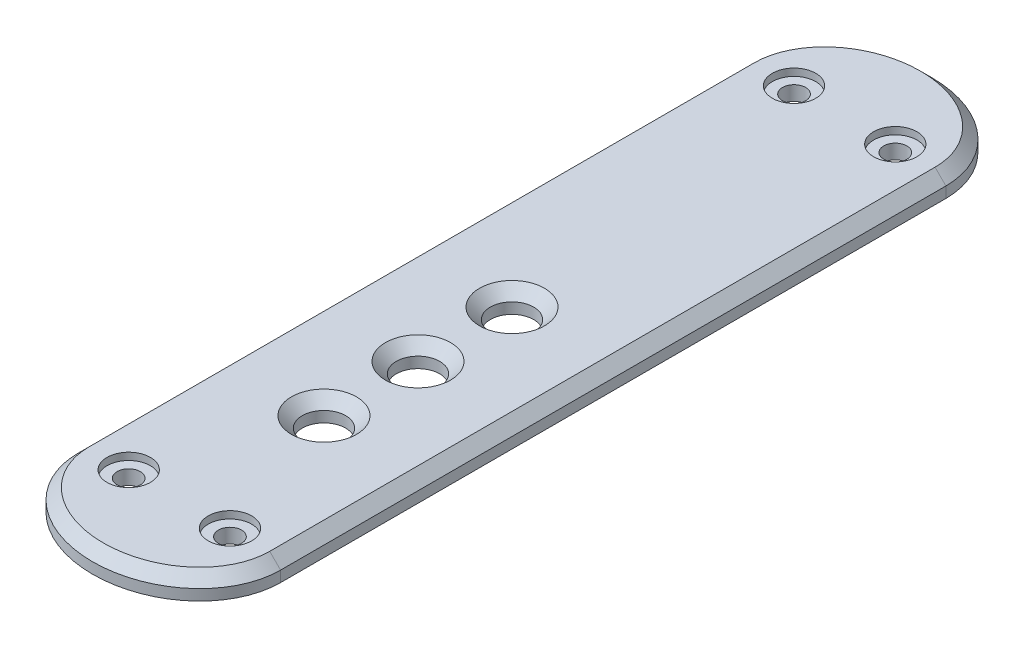
SolidWorks part; units mm, degrees
ref_plane "Front Plane" through (0, 0, 0) normal (0, 0, 1) x (1, 0, 0)
ref_plane "Top Plane" through (0, 0, 0) normal (0, 1, 0) x (1, 0, 0)
ref_plane "Right Plane" through (0, 0, 0) normal (1, 0, 0) x (0, 0, -1)
sketch "Sketch3" plane through (0, 0, 0) normal (0, 1, 0) x (1, 0, 0)
  line L0 (-7, 0) -> (7, 0) construction
  line L4 (-7, -23) -> (-7, 23)
  line L5 (0, -29) -> (0, 29) construction
  line L6 (7, -23) -> (7, 23)
  circle A0 centre (-3.5, 23) radius 0.8
  circle A1 centre (-3.5, 23) radius 1.5
  circle A2 centre (3.5, 23) radius 1.5
  circle A3 centre (3.5, 23) radius 0.8
  circle A4 centre (3.5, -23) radius 0.8
  circle A5 centre (3.5, -23) radius 1.5
  circle A6 centre (-3.5, -23) radius 1.5
  circle A7 centre (-3.5, -23) radius 0.8
  ellipse E0 centre (0, 23) end of major axis (-7, 23) minor radius 6 (7, 23) -> (-7, 23) ccw
  ellipse E1 centre (0, -23) end of major axis (-7, -23) minor radius 6 (7, -23) -> (-7, -23) cw
  point P20 (0, 0)
  dimension "D1" = 1.6
  dimension "D6" = 3
  dimension "D2" = 3.5
  dimension "D3" = 23
  dimension "D4" = 29
  dimension "D5" = 7
extrude "Boss-Extrude2" add sketch "Sketch3" against normal blind 1.5 contours L4 E0 L6 E1
extrude "Cut-Extrude1" cut sketch "Sketch3<3>" against normal through all contours A7 | A4 | A0 | A3
sketch "Sketch3<3>" plane through (0, 0, 0) normal (0, 1, 0) x (1, 0, 0) same geometry as "Sketch3"
extrude "Cut-Extrude4" cut sketch "Sketch3<4>" against normal blind 0.5 contours A1 | A2 | A6 | A5
sketch "Sketch3<4>" plane through (0, 0, 0) normal (0, 1, 0) x (1, 0, 0) same geometry as "Sketch3"
chamfer "Chamfer2" distance 0.75 angle 45 4 edges at (7, 0, 0) (0, 0, 29) (0, 0, -29) (-7, 0, 0)
sketch "Sketch6" plane through (0, 0, 0) normal (0, 1, 0) x (1, 0, 0)
  line L0 (0, 11.45) -> (0, 14.1085)
  line L1 (0.2205, 14.1892) -> (1.4045, 12.7884)
  line L2 (1.5955, 12.7884) -> (2.7795, 14.1892)
  line L3 (3, 14.1085) -> (3, 11.45)
  line L4 (-2.9, 11.45) -> (3, 11.45) construction
  line L13 (-3.5, 21.5) -> (3.5, 21.5) construction
  line L14 (3.5, 21.5) -> (0, 21.5) construction
  line L15 (0, 21.5) -> (0, 0) construction
  circle A0 centre (0, 12.2) radius 4.5
  arc A2 (-3, 11.45) -> (0, 11.45) centre (-1.5, 11.45) ccw
  arc A3 (3, 14.1085) -> (2.7795, 14.1892) centre (2.875, 14.1085) ccw
  arc A4 (1.5955, 12.7884) -> (1.4045, 12.7884) centre (1.5, 12.8691) cw
  arc A5 (0.2205, 14.1892) -> (0, 14.1085) centre (0.125, 14.1085) ccw
  circle A17 centre (-3.5, 23) radius 1.5 construction
  circle A18 centre (3.5, 23) radius 1.5 construction
  circle A19 centre (-3.5, 23) radius 1.5 construction
  circle A20 centre (3.5, 23) radius 1.5 construction
  point P16 (3, 14.45)
  point P19 (1.5, 12.6755)
  point P22 (0, 14.45)
  dimension "D1" = 9
  dimension "D2" = 3
  dimension "D7" = 0.125
  dimension "D3" = 3
  dimension "D4" = 3
  dimension "D5" = 1.5
  dimension "D6" = 0.75
  dimension "D9" = 9.3
  dimension "D8" = 21.5
sketch "Sketch8" plane through (0, 0, 0) normal (0, 1, 0) x (1, 0, 0)
  line L0 (0, -29) -> (0, 29) construction
  line L1 (1.5, 0) -> (1.5, -13) construction
  line L2 (0, -1.5) -> (0, -5) construction
  line L3 (0, -5) -> (0, -8) construction
  line L4 (0, -8) -> (0, -11.5) construction
  line L5 (0, -11.5) -> (0, -14.5) construction
  circle A0 centre (0, 0) radius 1.5
  circle A1 centre (0, -6.5) radius 1.5
  circle A2 centre (0, -13) radius 1.5
  dimension "D1" = 1.5
  dimension "D2" = 3.5
  dimension "D3" = 3.5
extrude "Cut-Extrude5" cut sketch "Sketch8" against normal through all
chamfer "Chamfer3" distance 0.75 angle 45 3 edges at (0, 0, 14.5) (0, 0, 8) (0, 0, 1.5)
